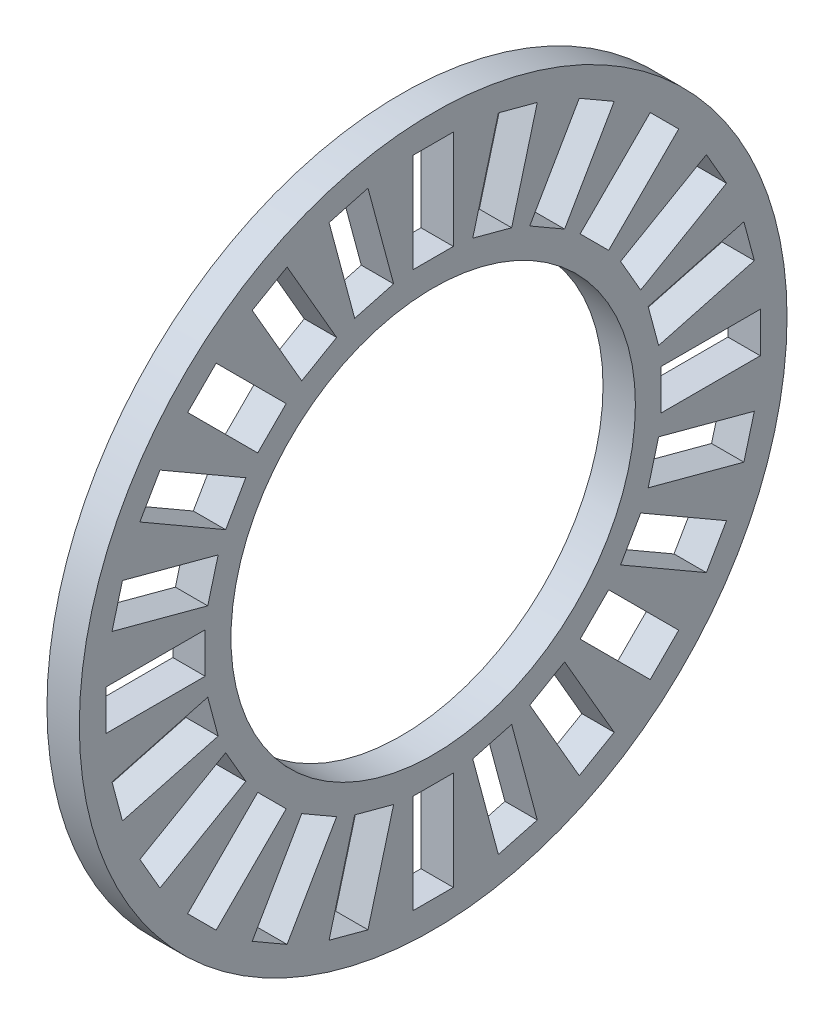
SolidWorks part; units mm, degrees
ref_plane "Front Plane" through (0, 0, 0) normal (0, 0, 1) x (1, 0, 0)
ref_plane "Top Plane" through (0, 0, 0) normal (0, 1, 0) x (1, 0, 0)
ref_plane "Right Plane" through (0, 0, 0) normal (1, 0, 0) x (0, 0, -1)
ref_plane "Plane1" through (0, 0, 0) normal (1, 0, 0) x (0, 0, -1)
sketch "Sketch1" plane through (0, 0, 0) normal (1, 0, 0) x (0, 0, -1)
  line L0 (11.275, 0.9961) -> (11.275, -0.9961)
  line L1 (11.275, -0.9961) -> (16.175, -0.9961)
  line L2 (16.175, -0.9961) -> (16.175, 0.9961)
  line L3 (16.175, 0.9961) -> (11.275, 0.9961)
  line L4 (10.633, 3.8803) -> (11.1486, 1.956)
  line L5 (11.1486, 1.956) -> (15.8817, 3.2242)
  line L6 (15.8817, 3.2242) -> (15.366, 5.1485)
  line L7 (15.366, 5.1485) -> (10.633, 3.8803)
  line L8 (10.633, -3.8803) -> (15.366, -5.1485)
  line L9 (15.366, -5.1485) -> (15.8817, -3.2242)
  line L10 (15.8817, -3.2242) -> (11.1486, -1.956)
  line L11 (11.1486, -1.956) -> (10.633, -3.8803)
  line L12 (9.2664, 6.5001) -> (10.2625, 4.7749)
  line L13 (10.2625, 4.7749) -> (14.506, 7.2249)
  line L14 (14.506, 7.2249) -> (13.5099, 8.9501)
  line L15 (13.5099, 8.9501) -> (9.2664, 6.5001)
  line L16 (9.2664, -6.5001) -> (13.5099, -8.9501)
  line L17 (13.5099, -8.9501) -> (14.506, -7.2249)
  line L18 (14.506, -7.2249) -> (10.2625, -4.7749)
  line L19 (10.2625, -4.7749) -> (9.2664, -6.5001)
  line L20 (7.2683, 8.677) -> (8.677, 7.2683)
  line L21 (8.677, 7.2683) -> (12.1418, 10.7331)
  line L22 (12.1418, 10.7331) -> (10.7331, 12.1418)
  line L23 (10.7331, 12.1418) -> (7.2683, 8.677)
  line L24 (7.2683, -8.677) -> (10.7331, -12.1418)
  line L25 (10.7331, -12.1418) -> (12.1418, -10.7331)
  line L26 (12.1418, -10.7331) -> (8.677, -7.2683)
  line L27 (8.677, -7.2683) -> (7.2683, -8.677)
  line L28 (4.7749, 10.2625) -> (6.5001, 9.2664)
  line L29 (6.5001, 9.2664) -> (8.9501, 13.5099)
  line L30 (8.9501, 13.5099) -> (7.2249, 14.506)
  line L31 (7.2249, 14.506) -> (4.7749, 10.2625)
  line L32 (4.7749, -10.2625) -> (7.2249, -14.506)
  line L33 (7.2249, -14.506) -> (8.9501, -13.5099)
  line L34 (8.9501, -13.5099) -> (6.5001, -9.2664)
  line L35 (6.5001, -9.2664) -> (4.7749, -10.2625)
  line L36 (1.956, 11.1486) -> (3.8803, 10.633)
  line L37 (3.8803, 10.633) -> (5.1485, 15.366)
  line L38 (5.1485, 15.366) -> (3.2242, 15.8817)
  line L39 (3.2242, 15.8817) -> (1.956, 11.1486)
  line L40 (1.956, -11.1486) -> (3.2242, -15.8817)
  line L41 (3.2242, -15.8817) -> (5.1485, -15.366)
  line L42 (5.1485, -15.366) -> (3.8803, -10.633)
  line L43 (3.8803, -10.633) -> (1.956, -11.1486)
  line L44 (-0.9961, 11.275) -> (0.9961, 11.275)
  line L45 (0.9961, 11.275) -> (0.9961, 16.175)
  line L46 (0.9961, 16.175) -> (-0.9961, 16.175)
  line L47 (-0.9961, 16.175) -> (-0.9961, 11.275)
  line L48 (-0.9961, -16.175) -> (0.9961, -16.175)
  line L49 (0.9961, -16.175) -> (0.9961, -11.275)
  line L50 (0.9961, -11.275) -> (-0.9961, -11.275)
  line L51 (-0.9961, -11.275) -> (-0.9961, -16.175)
  line L52 (-5.1485, 15.366) -> (-3.8803, 10.633)
  line L53 (-3.8803, 10.633) -> (-1.956, 11.1486)
  line L54 (-1.956, 11.1486) -> (-3.2242, 15.8817)
  line L55 (-3.2242, 15.8817) -> (-5.1485, 15.366)
  line L56 (-5.1485, -15.366) -> (-3.2242, -15.8817)
  line L57 (-3.2242, -15.8817) -> (-1.956, -11.1486)
  line L58 (-1.956, -11.1486) -> (-3.8803, -10.633)
  line L59 (-3.8803, -10.633) -> (-5.1485, -15.366)
  line L60 (-8.9501, 13.5099) -> (-6.5001, 9.2664)
  line L61 (-6.5001, 9.2664) -> (-4.7749, 10.2625)
  line L62 (-4.7749, 10.2625) -> (-7.2249, 14.506)
  line L63 (-7.2249, 14.506) -> (-8.9501, 13.5099)
  line L64 (-8.9501, -13.5099) -> (-7.2249, -14.506)
  line L65 (-7.2249, -14.506) -> (-4.7749, -10.2625)
  line L66 (-4.7749, -10.2625) -> (-6.5001, -9.2664)
  line L67 (-6.5001, -9.2664) -> (-8.9501, -13.5099)
  line L68 (-12.1418, 10.7331) -> (-8.677, 7.2683)
  line L69 (-8.677, 7.2683) -> (-7.2683, 8.677)
  line L70 (-7.2683, 8.677) -> (-10.7331, 12.1418)
  line L71 (-10.7331, 12.1418) -> (-12.1418, 10.7331)
  line L72 (-12.1418, -10.7331) -> (-10.7331, -12.1418)
  line L73 (-10.7331, -12.1418) -> (-7.2683, -8.677)
  line L74 (-7.2683, -8.677) -> (-8.677, -7.2683)
  line L75 (-8.677, -7.2683) -> (-12.1418, -10.7331)
  line L76 (-14.506, 7.2249) -> (-10.2625, 4.7749)
  line L77 (-10.2625, 4.7749) -> (-9.2664, 6.5001)
  line L78 (-9.2664, 6.5001) -> (-13.5099, 8.9501)
  line L79 (-13.5099, 8.9501) -> (-14.506, 7.2249)
  line L80 (-14.506, -7.2249) -> (-13.5099, -8.9501)
  line L81 (-13.5099, -8.9501) -> (-9.2664, -6.5001)
  line L82 (-9.2664, -6.5001) -> (-10.2625, -4.7749)
  line L83 (-10.2625, -4.7749) -> (-14.506, -7.2249)
  line L84 (-15.8817, 3.2242) -> (-11.1486, 1.956)
  line L85 (-11.1486, 1.956) -> (-10.633, 3.8803)
  line L86 (-10.633, 3.8803) -> (-15.366, 5.1485)
  line L87 (-15.366, 5.1485) -> (-15.8817, 3.2242)
  line L88 (-15.8817, -3.2242) -> (-15.366, -5.1485)
  line L89 (-15.366, -5.1485) -> (-10.633, -3.8803)
  line L90 (-10.633, -3.8803) -> (-11.1486, -1.956)
  line L91 (-11.1486, -1.956) -> (-15.8817, -3.2242)
  line L92 (-16.175, -0.9961) -> (-11.275, -0.9961)
  line L93 (-11.275, -0.9961) -> (-11.275, 0.9961)
  line L94 (-11.275, 0.9961) -> (-16.175, 0.9961)
  line L95 (-16.175, 0.9961) -> (-16.175, -0.9961)
  circle A0 centre (0, 0) radius 17.5
  circle A1 centre (0, 0) radius 10
extrude "Boss-Extrude1" add sketch "Sketch1" against normal blind 0.8 and the other way blind 0.8
